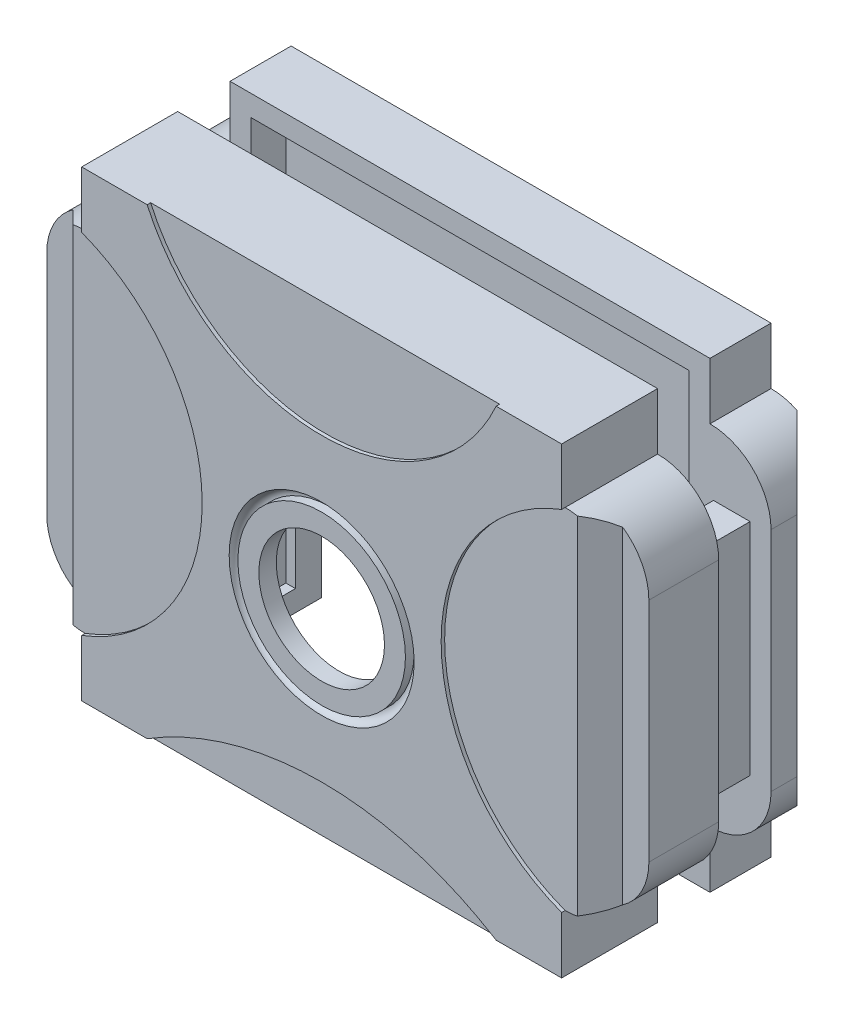
SolidWorks part; units mm, degrees
note: The reader was unsure of these and kept them because the rebuilt part matched: shared geometry of "Sketch1<3>", "Sketch2<3>", "Sketch5<3>", "Sketch5<4>".
ref_plane "Front Plane" through (0, 0, 0) normal (0, 0, 1) x (1, 0, 0)
ref_plane "Top Plane" through (0, 0, 0) normal (0, 1, 0) x (1, 0, 0)
ref_plane "Right Plane" through (0, 0, 0) normal (1, 0, 0) x (0, 0, -1)
sketch "Sketch1" plane through (0, 0, 0) normal (0, 0, 1) x (1, 0, 0)
  line L0 (-1.2, 1.2) -> (-1.2, -25.3)
  line L1 (0, 0) -> (25.1, 0)
  line L2 (0, 0) -> (0, -24.1)
  line L3 (0, -24.1) -> (25.1, -24.1)
  line L4 (25.1, 0) -> (25.1, -24.1)
  line L5 (8.3, -9.6) -> (16.8, -9.6) construction
  line L6 (8.3, -9.6) -> (8.3, -18.1) construction
  line L7 (8.3, -18.1) -> (16.8, -18.1) construction
  line L8 (16.8, -9.6) -> (16.8, -18.1) construction
  line L9 (-1.2, -25.3) -> (26.3, -25.3)
  line L10 (26.3, 1.2) -> (26.3, -25.3)
  line L11 (-1.2, 1.2) -> (26.3, 1.2)
  circle A0 centre (12.55, -13.85) radius 3.6
  point P9 (12.55, -18.1)
  point P10 (12.55, -24.1)
  point P14 (8.3, -13.85)
  point P16 (12.55, -9.6)
  dimension "D5" = 7.2
  dimension "D1" = 25.1
  dimension "D2" = 24.1
  dimension "D3" = 8.5
  dimension "D4" = 6
  dimension "D6" = 1.2
extrude "Boss-Extrude1" add sketch "Sketch1" against normal blind 1 contours L4 L1 L2 L3 A0
extrude "Boss-Extrude2" add sketch "Sketch1<3>" against normal blind 5.5 contours L11 L0 L9 L10 L1 L4 L3 L2
sketch "Sketch1<3>" plane through (0, 0, 0) normal (0, 0, 1) x (1, 0, 0) same geometry as "Sketch1"
sketch "Sketch2" plane through (0, 0, -5.5) normal (0, 0, -1) x (-1, 0, 0)
  line L0 (-26.3, 1.2) -> (-26.3, -25.3) construction
  line L1 (-29.8, -5.55) -> (-29.8, -18.55)
  line L2 (-25.1, -12.05) -> (0, -12.05) construction
  line L6 (-25.1, 0) -> (-25.1, -24.1) construction
  line L11 (0, 0) -> (0, -24.1) construction
  line L14 (-26.3, -5.55) -> (-28.8, -5.55)
  line L15 (-26.3, -5.55) -> (-26.3, -18.55)
  line L16 (-26.3, -18.55) -> (-28.8, -18.55)
  line L17 (-28.8, -5.55) -> (-28.8, -18.55)
  line L18 (-26.3, -2.05) -> (-26.3, -22.05)
  line L19 (-12.55, 0) -> (-12.55, -24.1) construction
  line L20 (0, 0) -> (-25.1, 0) construction
  line L21 (0, -24.1) -> (-25.1, -24.1) construction
  line L22 (1.2, -18.55) -> (3.7, -18.55)
  line L23 (1.2, -5.55) -> (3.7, -5.55)
  line L24 (3.7, -5.55) -> (3.7, -18.55)
  line L25 (4.7, -5.55) -> (4.7, -18.55)
  line L26 (1.2, -2.05) -> (1.2, -22.05)
  arc A1 (-26.3, -2.05) -> (-29.8, -5.55) centre (-26.3, -5.55) ccw
  arc A3 (-26.3, -22.05) -> (-29.8, -18.55) centre (-26.3, -18.55) cw
  arc A4 (1.2, -2.05) -> (4.7, -5.55) centre (1.2, -5.55) cw
  arc A5 (1.2, -22.05) -> (4.7, -18.55) centre (1.2, -18.55) ccw
  point P17 (-29.8, -12.05)
  dimension "D4" = 20
  dimension "D5" = 3.5
  dimension "D6" = 2.5
extrude "Boss-Extrude3" add sketch "Sketch2" against normal blind 3
extrude "Boss-Extrude4" add sketch "Sketch2<3>" against normal blind 1 from surface at -3
sketch "Sketch2<3>" plane through (0, 0, -5.5) normal (0, 0, -1) x (-1, 0, 0) same geometry as "Sketch2"
chamfer "Chamfer1" distance 2 angle 45 2 edges at (-1.2, -12.05, -1.5) (26.3, -12.05, -1.5)
sketch "Sketch3" plane through (0, 0, 0) normal (0, 0, 1) x (1, 0, 0)
  line L1 (12.55, -13.85) -> (12.55, -17.45) construction
  line L3 (12.55, -10.25) -> (12.55, -5.25) construction
  line L5 (12.55, -17.45) -> (12.55, -22.45) construction
  line L14 (12.55, -13.85) -> (5.55, -13.85) construction
  line L18 (-1.2, -2.05) -> (-5.3503, -2.05)
  line L19 (-5.3503, -2.05) -> (-5.3503, -22.05)
  line L20 (-5.3503, -22.05) -> (-1.2, -22.05)
  line L21 (30.4503, -22.05) -> (26.3, -22.05)
  line L22 (30.4503, -2.05) -> (30.4503, -22.05)
  line L23 (26.3, -2.05) -> (30.4503, -2.05)
  circle A1 centre (12.55, -13.85) radius 3.6 construction
  arc A3 (2.55, 1.2) -> (22.55, 1.2) centre (12.55, 5.7269) ccw
  arc A4 (2.55, -25.3) -> (22.55, -25.3) centre (12.55, -41.4189) cw
  arc A5 (-1.2, -2.05) -> (-1.2, -22.05) centre (-4.9924, -12.05) cw
  arc A7 (26.3, -2.05) -> (26.3, -22.05) centre (30.0924, -12.05) ccw
  point P6 (12.55, -13.85)
  line M9 (26.3, 1.2) -> (-1.2, 1.2)
  line M15 (-1.2, -25.3) -> (26.3, -25.3)
  arc M31 (-1.2, -2.05) -> (-1.7, -2.0859) centre (-1.2, -5.55) ccw
  line M32 (-1.7, -2.0859) -> (-1.7, -22.0141)
  arc M33 (-1.7, -22.0141) -> (-1.2, -22.05) centre (-1.2, -18.55) ccw
  arc M35 (26.3, -22.05) -> (26.8, -22.0141) centre (26.3, -18.55) ccw
  line M36 (26.8, -22.0141) -> (26.8, -2.0859)
  arc M37 (26.8, -2.0859) -> (26.3, -2.05) centre (26.3, -5.55) ccw
  dimension "D1" = 7
extrude "Cut-Extrude2" cut sketch "Sketch3" against normal blind 0.2 contours A5 M31 M32 M33 | A3 M9 | A7 M37 M35 M36 | A4 M15 | L19 L20 L18 M33 M32 M31 | L23 L21 L22 M37 M36 M35
sketch "Sketch4" plane through (0, 0, 0) normal (0, 0, 1) x (1, 0, 0)
  circle A1 centre (12.55, -13.85) radius 5.3
  circle A2 centre (12.55, -13.85) radius 4.8
  circle A3 centre (12.55, -13.85) radius 4.8
  dimension "D1" = 1.2
  dimension "D2" = 0.5
extrude "Cut-Extrude4" cut sketch "Sketch4" against normal blind 0.5 contours A1 A3
fillet "Fillet2" radius 0.5 1 edges at (17.85, -13.85, -0.5)
sketch "Sketch7" plane through (0, 0, -5.5) normal (0, 0, -1) x (-1, 0, 0)
  line L14 (-28.6, -18.35) -> (-26.5, -18.35)
  line L15 (-26.5, -18.35) -> (-26.5, -5.75)
  line L16 (-28.6, -5.75) -> (-28.6, -18.35)
  line L17 (-26.5, -5.75) -> (-28.6, -5.75)
  line L18 (-28.6, -18.35) -> (-26.5, -18.35)
  line L19 (-26.5, -18.35) -> (-26.5, -5.75)
  line L20 (-28.6, -5.75) -> (-28.6, -18.35)
  line L21 (-26.5, -5.75) -> (-28.6, -5.75)
  line L32 (1.4, -5.75) -> (1.4, -18.35)
  line L33 (1.4, -18.35) -> (3.5, -18.35)
  line L34 (3.5, -18.35) -> (3.5, -5.75)
  line L35 (3.5, -5.75) -> (1.4, -5.75)
  line L36 (1.4, -5.75) -> (1.4, -18.35)
  line L37 (1.4, -18.35) -> (3.5, -18.35)
  line L38 (3.5, -18.35) -> (3.5, -5.75)
  line L39 (3.5, -5.75) -> (1.4, -5.75)
  dimension "D1" = 0.2
  dimension "D2" = 0.2
sketch "Sketch5" plane through (0, 0, -5.5) normal (0, 0, -1) x (-1, 0, 0)
  line L14 (-25.1, -24.1) -> (0, -24.1)
  line L15 (0, -24.1) -> (0, 0)
  line L16 (0, 0) -> (-25.1, 0)
  line L17 (-25.1, 0) -> (-25.1, -24.1)
  line L18 (-25.1, -24.1) -> (0, -24.1)
  line L19 (0, -24.1) -> (0, 0)
  line L20 (0, 0) -> (-25.1, 0)
  line L21 (-25.1, 0) -> (-25.1, -24.1)
  line L53 (-26.3, -2.05) -> (-26.3, -22.05)
  line L54 (1.2, -2.05) -> (1.2, -22.05)
  line L61 (1.2, -2.05) -> (1.2, 1.2)
  line L62 (4.7, -18.55) -> (4.7, -5.55)
  line L63 (1.2, -25.3) -> (1.2, -22.05)
  line L64 (-26.3, -25.3) -> (1.2, -25.3)
  line L65 (-26.3, -22.05) -> (-26.3, -25.3)
  line L66 (-29.8, -5.55) -> (-29.8, -18.55)
  line L67 (-26.3, 1.2) -> (-26.3, -2.05)
  line L68 (1.2, 1.2) -> (-26.3, 1.2)
  line L69 (1.2, -2.05) -> (1.2, 1.2)
  line L70 (4.7, -18.55) -> (4.7, -5.55)
  line L71 (1.2, -25.3) -> (1.2, -22.05)
  line L72 (-26.3, -25.3) -> (1.2, -25.3)
  line L73 (-26.3, -22.05) -> (-26.3, -25.3)
  line L74 (-29.8, -5.55) -> (-29.8, -18.55)
  line L75 (-26.3, 1.2) -> (-26.3, -2.05)
  line L76 (1.2, 1.2) -> (-26.3, 1.2)
  arc A29 (4.7, -5.55) -> (1.2, -2.05) centre (1.2, -5.55) ccw
  arc A30 (1.2, -22.05) -> (4.7, -18.55) centre (1.2, -18.55) ccw
  arc A31 (-29.8, -18.55) -> (-26.3, -22.05) centre (-26.3, -18.55) ccw
  arc A32 (-26.3, -2.05) -> (-29.8, -5.55) centre (-26.3, -5.55) ccw
  arc A33 (4.7, -5.55) -> (1.2, -2.05) centre (1.2, -5.55) ccw
  arc A34 (1.2, -22.05) -> (4.7, -18.55) centre (1.2, -18.55) ccw
  arc A35 (-29.8, -18.55) -> (-26.3, -22.05) centre (-26.3, -18.55) ccw
  arc A36 (-26.3, -2.05) -> (-29.8, -5.55) centre (-26.3, -5.55) ccw
  line M17 (3.7, -18.55) -> (1.2, -18.55)
  line M18 (1.2, -18.55) -> (1.2, -5.55)
  line M19 (1.2, -5.55) -> (3.7, -5.55)
  line M20 (3.7, -5.55) -> (3.7, -18.55)
  line M21 (-28.8, -5.55) -> (-26.3, -5.55)
  line M22 (-26.3, -5.55) -> (-26.3, -18.55)
  line M23 (-26.3, -18.55) -> (-28.8, -18.55)
  line M24 (-28.8, -18.55) -> (-28.8, -5.55)
  line M25 (1.2, 1.2) -> (-26.3, 1.2)
  line M26 (-26.3, 1.2) -> (-26.3, -2.05)
  arc M27 (-26.3, -2.05) -> (-29.8, -5.55) centre (-26.3, -5.55) ccw
  line M28 (-29.8, -5.55) -> (-29.8, -18.55)
  arc M29 (-29.8, -18.55) -> (-26.3, -22.05) centre (-26.3, -18.55) ccw
  line M30 (-26.3, -22.05) -> (-26.3, -25.3)
  line M31 (-26.3, -25.3) -> (1.2, -25.3)
  line M32 (1.2, -25.3) -> (1.2, -22.05)
  arc M33 (1.2, -22.05) -> (4.7, -18.55) centre (1.2, -18.55) ccw
  line M34 (4.7, -18.55) -> (4.7, -5.55)
  arc M35 (4.7, -5.55) -> (1.2, -2.05) centre (1.2, -5.55) ccw
  line M36 (1.2, -2.05) -> (1.2, 1.2)
  line M37 (-25.1, 0) -> (0, 0)
  line M38 (0, 0) -> (0, -24.1)
  line M39 (0, -24.1) -> (-25.1, -24.1)
  line M40 (-25.1, -24.1) -> (-25.1, 0)
  dimension "D2" = 0
  dimension "D1" = 0
extrude "Boss-Extrude5" add sketch "Sketch5" along normal blind 2 from offset 3 contours L54 L53 M36 M25 M26 M22 M30 M31 M32 M18 M40 M37 M38 M39 | A34 L70 A33
extrude "Boss-Extrude6" add sketch "Sketch5<3>" along normal blind 1.5 from surface at 3 contours L54 M35 M19 M20 M17 M33 M34 | L53 M27 M28 M29 M23 M24 M21 | M17 M20 M19 M18 | M21 M24 M23 M22 starting at face at (12.55, -12.05, -8.5)
sketch "Sketch5<3>" plane through (0, 0, -5.5) normal (0, 0, -1) x (-1, 0, 0) same geometry as "Sketch5"
extrude "Boss-Extrude7" add sketch "Sketch5<4>" along normal blind 1.5 from surface at 5 contours M37 M40 M39 M38 | L54 L53 M36 M25 M26 M22 M30 M31 M32 M18 M40 M37 M38 M39 starting at face at (12.55, -12.05, -10.5)
sketch "Sketch5<4>" plane through (0, 0, -5.5) normal (0, 0, -1) x (-1, 0, 0) same geometry as "Sketch5"
sketch "Sketch6" plane through (0, 0, -12) normal (0, 0, -1) x (-1, 0, 0)
  line L0 (1.2, -25.3) -> (-26.3, -25.3) construction
  line L1 (-24.55, -18.8) -> (-0.55, -18.8)
  line L2 (-24.55, -18.8) -> (-24.55, -25.3)
  line L3 (-24.55, -25.3) -> (-0.55, -25.3)
  line L4 (-0.55, -18.8) -> (-0.55, -25.3)
  line L5 (-26.3, 1.2) -> (1.2, 1.2) construction
  point P6 (-12.55, -18.8)
  point P9 (-12.55, 1.2)
  dimension "D1" = 24
  dimension "D2" = 6.5
extrude "Cut-Extrude5" cut sketch "Sketch6" against normal up to next
chamfer "Chamfer2" distance 3.5 angle 45 2 edges at (26.3, -12.05, -10) (-1.2, -12.05, -10)
extrude "Boss-Extrude9" add sketch "Sketch7" against normal blind 2.5 from surface at 3 starting at face at (12.55, -14.58, -8.5)
sketch "Sketch8" plane through (0, 0, -12) normal (0, 0, -1) x (-1, 0, 0)
  line L0 (-12.55, 1.2) -> (-12.55, -18.8) construction
  line L1 (-26.3, 1.2) -> (1.2, 1.2) construction
  line L2 (-0.55, -18.8) -> (-24.55, -18.8) construction
  line L4 (-20.05, -5.3) -> (-5.05, -5.3)
  line L5 (-20.05, -5.3) -> (-20.05, -6.6)
  line L6 (-20.05, -6.6) -> (-5.05, -6.6)
  line L7 (-5.05, -5.3) -> (-5.05, -6.6)
  line L8 (-20.05, -11.6) -> (-5.05, -11.6)
  line L9 (-20.05, -11.6) -> (-20.05, -12.9)
  line L10 (-20.05, -12.9) -> (-5.05, -12.9)
  line L11 (-5.05, -11.6) -> (-5.05, -12.9)
  point P14 (-12.55, -6.6)
  dimension "D1" = 15
  dimension "D2" = 1.3
  dimension "D3" = 5
  dimension "D4" = 6.5
extrude "Cut-Extrude6" cut sketch "Sketch8" against normal blind 1
chamfer "Chamfer3" distance 0.3 angle 45 8 edges at (20.05, -12.25, -12) (12.55, -11.6, -12) (5.05, -12.25, -12) (12.55, -12.9, -12) (12.55, -5.3, -12) (20.05, -5.95, -12) (12.55, -6.6, -12) (5.05, -5.95, -12)
